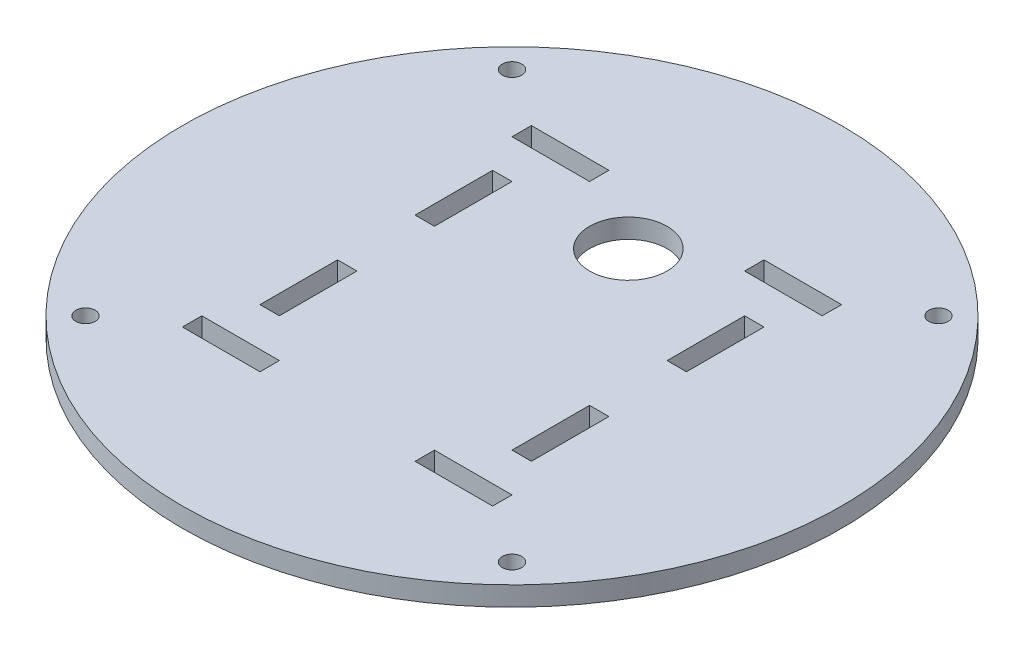
SolidWorks part; units mm, degrees
material "Pine"
ref_plane "Front Plane" through (0, 0, 0) normal (0, 0, 1) x (1, 0, 0)
ref_plane "Top Plane" through (0, 0, 0) normal (0, 1, 0) x (1, 0, 0)
ref_plane "Right Plane" through (0, 0, 0) normal (1, 0, 0) x (0, 0, -1)
sketch "Sketch1" plane through (0, 0, 0) normal (0, 1, 0) x (1, 0, 0)
  line L0 (0, 0) -> (0, 123.9148) construction
  line L1 (0, 0) -> (144.4711, 0) construction
  line L2 (-50.8, 50.8) -> (-25.4, 50.8)
  line L3 (-50.8, 50.8) -> (-50.8, 57.15)
  line L4 (-50.8, 57.15) -> (-25.4, 57.15)
  line L5 (-25.4, 50.8) -> (-25.4, 57.15)
  line L6 (25.4, 50.8) -> (25.4, 57.15)
  line L7 (50.8, 57.15) -> (25.4, 57.15)
  line L8 (50.8, 50.8) -> (50.8, 57.15)
  line L9 (50.8, 50.8) -> (25.4, 50.8)
  line L10 (-25.4, -50.8) -> (-25.4, -57.15)
  line L11 (-50.8, -50.8) -> (-25.4, -50.8)
  line L12 (-50.8, -50.8) -> (-50.8, -57.15)
  line L13 (-50.8, -57.15) -> (-25.4, -57.15)
  line L14 (50.8, -50.8) -> (50.8, -57.15)
  line L15 (50.8, -57.15) -> (25.4, -57.15)
  line L16 (25.4, -50.8) -> (25.4, -57.15)
  line L17 (50.8, -50.8) -> (25.4, -50.8)
  line L18 (38.1, -38.1) -> (44.45, -38.1)
  line L19 (38.1, 38.1) -> (44.45, 38.1)
  line L20 (38.1, 38.1) -> (38.1, 12.7)
  line L21 (38.1, 12.7) -> (44.45, 12.7)
  line L22 (44.45, 38.1) -> (44.45, 12.7)
  line L23 (38.1, -38.1) -> (38.1, -12.7)
  line L24 (38.1, -12.7) -> (44.45, -12.7)
  line L25 (44.45, -38.1) -> (44.45, -12.7)
  line L26 (-38.1, -38.1) -> (-44.45, -38.1)
  line L27 (-44.45, -38.1) -> (-44.45, -12.7)
  line L28 (-38.1, -38.1) -> (-38.1, -12.7)
  line L29 (-38.1, -12.7) -> (-44.45, -12.7)
  line L30 (-38.1, 12.7) -> (-44.45, 12.7)
  line L31 (-38.1, 38.1) -> (-38.1, 12.7)
  line L32 (-38.1, 38.1) -> (-44.45, 38.1)
  line L33 (-44.45, 38.1) -> (-44.45, 12.7)
  circle A0 centre (0, 0) radius 107.95
  circle A1 centre (0, 38.1) radius 12.7
  dimension "D1" = 215.9
  dimension "D10" = 25.4
  dimension "D2" = 25.4
  dimension "D3" = 25.4
  dimension "D4" = 6.35
  dimension "D5" = 50.8
  dimension "D6" = 6.35
  dimension "D7" = 25.4
  dimension "D8" = 12.7
  dimension "D9" = 38.1
  dimension "D11" = 38.1
extrude "Boss-Extrude1" add sketch "Sketch1" along normal blind 6.35
sketch "Sketch2" plane through (0, 0, 0) normal (0, -1, 0) x (1, 0, 0)
  line L0 (0, 0) -> (0, 99.3828) construction
  line L1 (0, 0) -> (-150.0844, 0) construction
  circle A0 centre (-69.85, 69.85) radius 3.175
  circle A1 centre (69.85, 69.85) radius 3.175
  circle A2 centre (69.85, -69.85) radius 3.175
  circle A3 centre (-69.85, -69.85) radius 3.175
  dimension "D1" = 6.35
extrude "Cut-Extrude1" cut sketch "Sketch2" against normal up to surface (6.35 mm away) up to face at (-41.275, 6.35, -25.4)
